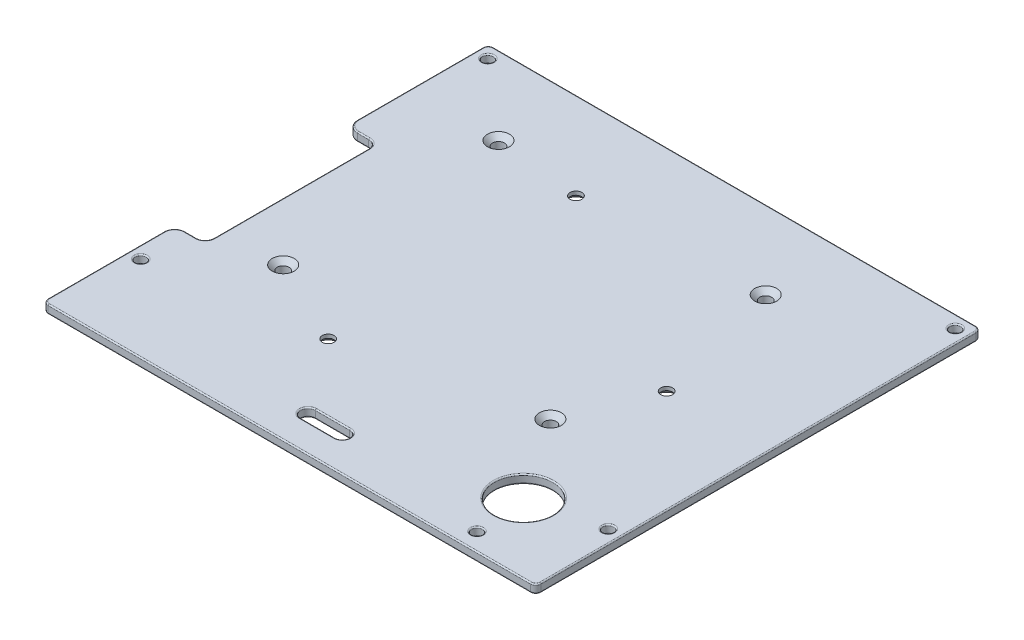
SolidWorks part; units mm, degrees
ref_plane "Front" through (0, 0, 0) normal (0, 0, 1) x (1, 0, 0)
ref_plane "Top" through (0, 0, 0) normal (0, 1, 0) x (1, 0, 0)
ref_plane "Right" through (0, 0, 0) normal (1, 0, 0) x (0, 0, -1)
sketch "Sketch1" plane through (0, 0, 0) normal (0, 1, 0) x (1, 0, 0)
  line L0 (74.1139, -65.7208) -> (-64.1571, -65.7208)
  line L1 (75.6139, -64.2208) -> (75.6139, 60.4235)
  line L2 (-65.6571, -64.2208) -> (-65.6571, 60.4235)
  line L3 (74.1139, 61.9235) -> (-64.1571, 61.9235)
  arc A0 (-64.1571, -65.7208) -> (-65.6571, -64.2208) centre (-64.1571, -64.2208) cw
  arc A1 (75.6139, -64.2208) -> (74.1139, -65.7208) centre (74.1139, -64.2208) cw
  arc A2 (75.6139, 60.4235) -> (74.1139, 61.9235) centre (74.1139, 60.4235) ccw
  arc A3 (-65.6571, 60.4235) -> (-64.1571, 61.9235) centre (-64.1571, 60.4235) cw
  dimension "D1" = 1.5
extrude "Boss-Extrude1" add sketch "Sketch1" against normal blind 2.5 from offset 5.5 offset against normal yes
ref_plane "Plane1" through (0, -8, 0) normal (0, -1, 0) x (-1, 0, 0)
sketch "Sketch2" plane through (0, -8, 0) normal (0, -1, 0) x (-1, 0, 0)
  line L0 (-0.2082, -55.5954) -> (-10.0277, -55.5954) construction
  line L1 (-0.2082, -57.7204) -> (-10.0277, -57.7204)
  line L2 (-0.2082, -53.4704) -> (-10.0277, -53.4704)
  line L3 (65.6571, 60.4235) -> (65.6571, -64.2208) construction
  line L4 (65.6571, -27.9769) -> (59.384, -27.9769)
  line L5 (65.6571, -27.9769) -> (65.6571, 21.4017)
  line L6 (65.6571, 21.4017) -> (59.384, 21.4017)
  line L7 (56.884, -25.4769) -> (56.884, 18.9017)
  circle A0 centre (62.1301, -41.2198) radius 1.55
  circle A1 centre (-71.8699, -41.2198) radius 1.55
  circle A2 centre (-71.8699, 58.2802) radius 1.55
  circle A3 centre (62.1301, 58.2802) radius 1.55
  circle A5 centre (-53.6527, -60.6149) radius 1.55
  circle A6 centre (-52.0625, -45.661) radius 8.35
  arc A7 (-0.2082, -57.7204) -> (-0.2082, -53.4704) centre (-0.2082, -55.5954) ccw
  arc A8 (-10.0277, -53.4704) -> (-10.0277, -57.7204) centre (-10.0277, -55.5954) ccw
  circle A9 centre (-36.33, 39.4767) radius 0.25
  circle A10 centre (40.27, 39.4767) radius 0.25
  circle A11 centre (40.27, -22.2433) radius 0.25
  arc A13 (59.384, 21.4017) -> (56.884, 18.9017) centre (59.384, 18.9017) ccw
  arc A14 (59.384, -27.9769) -> (56.884, -25.4769) centre (59.384, -25.4769) cw
  circle A15 centre (-36.33, -22.2433) radius 0.25 [skipped]
  circle A16 centre (-36.33, -22.2433) radius 0.25
  point P20 (-5.118, -55.5954)
  dimension "D1" = 2
  dimension "D3" = 2
  dimension "D5" = 2.5
  dimension "D2" = 2
  dimension "D4" = 2
extrude "Cut-Extrude5" cut sketch "Sketch2" against normal blind 2.5
fillet "Fillet1" radius 0.35 56 edges at (-65.6571, -5.5, 46.0988) (-65.6571, -5.5, -40.9126) (-65.2177, -5.5, -61.4841) (4.9784, -5.5, -61.9235) (75.1745, -5.5, -61.4841) (75.6139, -5.5, 1.8986) (75.1745, -5.5, 65.2814) (4.9784, -5.5, 65.7208) (-65.2177, -5.5, 65.2814) (-62.1301, -5.5, 39.6698) (52.0625, -5.5, 37.311) (53.6527, -5.5, 59.0649) (-62.1301, -5.5, -59.8302) (71.8699, -5.5, -59.8302) (71.8699, -5.5, 39.6698) (4.9784, -8, 65.7208) (75.1745, -8, 65.2814) (75.6139, -8, 1.8986) (75.1745, -8, -61.4841) (4.9784, -8, -61.9235) (-65.2177, -8, -61.4841) (-65.6571, -8, -40.9126) (-65.6571, -8, 46.0988) (-65.2177, -8, 65.2814) (-62.1301, -8, 39.6698) (52.0625, -8, 37.311) (53.6527, -8, 59.0649) (-62.1301, -8, -59.8302) (71.8699, -8, -59.8302) (71.8699, -8, 39.6698) (12.1527, -5.5, 55.5954) (5.118, -5.5, 53.4704) (-1.9168, -5.5, 55.5954) (5.118, -5.5, 57.7204) (5.118, -8, 53.4704) (12.1527, -8, 55.5954) (5.118, -8, 57.7204) (-1.9168, -8, 55.5954) (-40.27, -5.5, 21.9933) (-40.27, -5.5, -39.7267) (36.33, -5.5, -39.7267) (-40.27, -8, 21.9933) (-40.27, -8, -39.7267) (36.33, -8, -39.7267) (-62.5206, -5.5, -21.4017) (-62.5206, -5.5, 27.9769) (-56.884, -5.5, 3.2876) (-62.5206, -8, -21.4017) (-56.884, -8, 3.2876) (-62.5206, -8, 27.9769) (-57.6163, -5.5, -20.6695) (-57.6163, -5.5, 27.2447) (-57.6163, -8, -20.6695) (-57.6163, -8, 27.2447) (36.33, -5.5, 21.9933) (36.33, -8, 21.9933)
hole_wizard "CSK for M3 Flat Head Machine Screw1" positions "Sketch5" profile "Sketch6" countersink size "M3" standard "ANSI Metric" end condition through all
sketch "Sketch5" plane through (0, -5.5, 0) normal (0, 1, 0) x (1, 0, 0)
  point P0 (36.33, 39.4767)
  point P6 (-40.27, 39.4767)
  point P9 (-40.27, -22.2433)
  point P12 (36.33, -22.2433)
sketch "Sketch6" plane through (36.33, -5.5, -39.4767) normal (1, 0, 0) x (0, 0, 1)
  line L0 (0, 0) -> (0, 2.5)
  line L1 (0, 2.5) -> (1.7, 2.5)
  line L2 (1.7, 2.5) -> (1.7, 1.45)
  line L3 (1.7, 1.45) -> (3.15, 0)
  line L5 (3.15, 0) -> (0, 0)
  line L6 (-1.7, 1.45) -> (-3.15, 0) construction
  line L11 (0, -6.35) -> (0, 107.95) construction
  dimension "Thru Hole Dia." = 3.4
  dimension "Thru Hole Depth" = 2.5
  dimension "Near C'Sink Dia." = 6.3
  dimension "Near C'Sink Angle" = 90
ref_plane "Plane2" through (0, -5.5, 0) normal (0, 1, 0) x (1, 0, 0)
sketch "Sketch9" plane through (0, -5.5, 0) normal (0, 1, 0) x (1, 0, 0)
  line L0 (5.0737, 1.3278) -> (46.0737, 1.3278) construction
  line L1 (5.0737, 1.3278) -> (-15.4263, 36.8348) construction
  line L2 (5.0737, 1.3278) -> (-15.4263, -34.1793) construction
  circle A1 centre (46.0737, 1.3278) radius 0.25
  circle A2 centre (-15.4263, -34.1793) radius 0.25
  circle A3 centre (-15.4263, 36.8348) radius 0.25
  point P12 (5.0737, 1.3278)
  dimension "D1" = 3
extrude "Cut-Extrude7" cut sketch "Sketch9" against normal through all
hole_wizard "CSK for M3 Flat Head Machine Screw2" positions "Sketch14" profile "Sketch15" countersink size "M3" standard "ANSI Metric" end condition through all
sketch "Sketch14" plane through (0, -8, 0) normal (0, -1, 0) x (-1, 0, 0)
  point P0 (15.4263, -34.1793)
  point P3 (-46.0737, 1.3278)
  point P6 (15.4263, 36.8348)
sketch "Sketch15" plane through (-15.4263, -8, 34.1793) normal (1, 0, 0) x (0, 0, -1)
  line L0 (0, 0) -> (0, 2.5)
  line L1 (0, 2.5) -> (1.7, 2.5)
  line L2 (1.7, 2.5) -> (1.7, 1.45)
  line L3 (1.7, 1.45) -> (3.15, 0)
  line L5 (3.15, 0) -> (0, 0)
  line L6 (-1.7, 1.45) -> (-3.15, 0) construction
  line L11 (0, -6.35) -> (0, 107.95) construction
  dimension "Thru Hole Dia." = 3.4
  dimension "Thru Hole Depth" = 2.5
  dimension "Near C'Sink Dia." = 6.3
  dimension "Near C'Sink Angle" = 90
fillet "Fillet2" radius 3 6 edges at (-65.5546, -7.8975, 28.0794) (-65.5546, -5.6025, 28.0794) (-65.5546, -7.8975, -21.5042) (-65.5546, -5.6025, -21.5042) (-65.6571, -6.75, -21.4017) (-65.6571, -6.75, 27.9769)
sketch "Sketch17" plane through (0, -8, 0) normal (0, -1, 0) x (-1, 0, 0)
  circle A0 centre (-36.33, 39.4767) radius 4.5
  circle A1 centre (-36.33, 39.4767) radius 1.7
  circle A2 centre (40.27, 39.4767) radius 4.5
  circle A3 centre (40.27, 39.4767) radius 1.7
  circle A4 centre (40.27, -22.2433) radius 4.5
  circle A5 centre (40.27, -22.2433) radius 1.7
  circle A6 centre (-36.33, -22.2433) radius 4.5
  circle A7 centre (-36.33, -22.2433) radius 1.7
  dimension "D1" = 2
  dimension "D2" = 2
extrude "Boss-Extrude2" add sketch "Sketch17" along normal blind 5
fillet "Fillet3" radius 3 4 edges at (36.33, -8, 17.7433) (-40.27, -8, 17.7433) (-40.27, -8, -43.9767) (36.33, -8, -43.9767)
